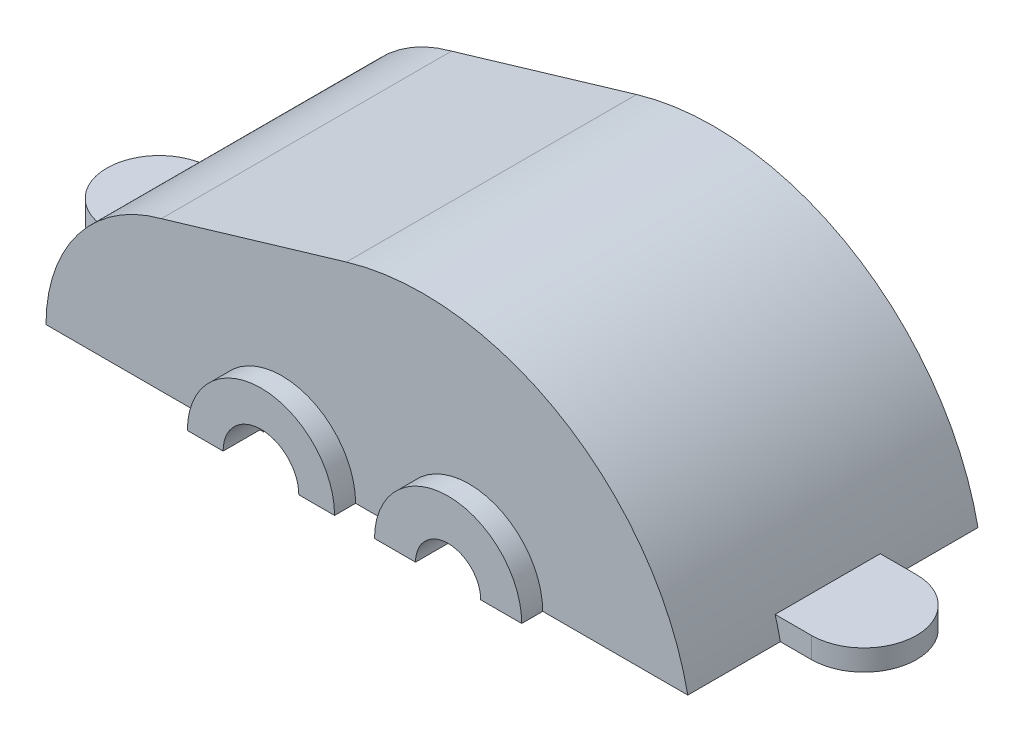
SolidWorks part; units mm, degrees
material "1023 Carbon Steel Sheet (SS)"
ref_plane "Front Plane" through (0, 0, 0) normal (0, 0, 1) x (1, 0, 0)
ref_plane "Top Plane" through (0, 0, 0) normal (0, 1, 0) x (1, 0, 0)
ref_plane "Right Plane" through (0, 0, 0) normal (1, 0, 0) x (0, 0, -1)
sketch "Sketch1" plane through (0, 0, 0) normal (0, 0, 1) x (1, 0, 0)
  line L0 (-31.8564, 122.8324) -> (144.4957, 175.1984)
  line L1 (443.1039, 0) -> (-126.8961, 0)
  line L2 (443.1039, 0) -> (443.1039, 185) construction
  line L3 (443.1039, 185) -> (-126.8961, 185) construction
  line L4 (-126.8961, 185) -> (-126.8961, 0) construction
  arc A0 (-31.8564, 122.8324) -> (-126.8961, 0) centre (0, 0) ccw
  arc A1 (144.4957, 175.1984) -> (443.1039, 0) centre (211.938, -51.9261) cw
  dimension "D1" = 570
  dimension "D2" = 185
extrude "Boss-Extrude1" add sketch "Sketch1" along normal blind 236
shell "Shell1" thickness 20 removed face at (158.1039, 0, 118) outward yes
sketch "Sketch7" plane through (0, 0, 0) normal (0, -1, 0) x (1, 0, 0)
  line L0 (-335.2707, 118) -> (457.2585, 118) construction
  line L1 (-126.8961, 236) -> (443.1039, 236) construction
  line L2 (144.4957, 0) -> (-31.8564, 0) construction
  line L3 (-126.8961, 168) -> (-126.8961, 68.2794)
  line L4 (543.1039, 168) -> (443.1039, 168)
  line L5 (-126.8961, 236) -> (-126.8961, 0) construction
  line L6 (-126.8961, 68.2794) -> (-226.8961, 68.2794)
  line L7 (-226.8961, 68.2794) -> (-226.8961, 168)
  line L8 (-226.8961, 168) -> (-126.8961, 168)
  line L10 (543.1039, 168) -> (543.1039, 68)
  line L11 (443.1039, 236) -> (443.1039, 0) construction
  line L12 (443.1039, 168) -> (443.1039, 68)
  line L13 (443.1039, 68) -> (543.1039, 68)
  dimension "D1" = 100
  dimension "D2" = 100
  dimension "D3" = 100
  dimension "D4" = 100
extrude "Boss-Extrude2" add sketch "Sketch7" against normal blind 20
fillet "Fillet2" 2 edges at (-226.8961, 10, 168) (-226.8961, 10, 68.2794) type full round first side face at (-186.6396, 10.0058, 168) second side face at (-186.6396, 10.0058, 68.2794) middle face at (-226.8961, 10, 118.1397)
sketch "Sketch8" plane through (0, 0, -20) normal (0, 0, -1) x (-1, 0, 0)
  line L0 (146.8961, 0) -> (-463.5621, 0) construction
  line L1 (-41.5621, 0) -> (-113.5621, 0)
  line L2 (-219.5621, 0) -> (-291.5621, 0)
  arc A0 (-219.5621, 0) -> (-291.5621, 0) centre (-255.5621, 0) ccw
  arc A1 (-41.5621, 0) -> (-113.5621, 0) centre (-77.5621, 0) ccw
  dimension "D3" = 72
  dimension "D4" = 72
  dimension "D1" = 208
  dimension "D2" = 178
sketch "Sketch9" plane through (0, 0, 256) normal (0, 0, 1) x (1, 0, 0)
  line L0 (-146.8961, 0) -> (463.5621, 0) construction
  line L1 (286.5621, 0) -> (224.5621, 0)
  line L2 (113.5621, 0) -> (41.5621, 0)
  arc A0 (286.5621, 0) -> (224.5621, 0) centre (255.5621, 0) ccw
  arc A1 (113.5621, 0) -> (41.5621, 0) centre (77.5621, 0) ccw
  dimension "D1" = 72
  dimension "D2" = 62
  dimension "D3" = 208
  dimension "D4" = 178
extrude "Cut-Extrude1" cut sketch "Sketch8" against normal blind 20
extrude "Cut-Extrude2" cut sketch "Sketch9" against normal blind 20
fillet "Fillet3" 2 edges at (543.1039, 10, 168) (543.1039, 10, 68) type full round first side face at (502.1403, 10.0125, 168) second side face at (502.1403, 10.0125, 68) middle face at (543.1039, 10, 118)
sketch "Sketch10" plane through (0, 0, -20) normal (0, 0, -1) x (-1, 0, 0)
  line L0 (-185.5621, 0) -> (-219.5621, 0)
  line L1 (-291.5621, 0) -> (-325.5621, 0)
  arc A0 (-185.5621, 0) -> (-325.5621, 0) centre (-255.5621, 0) ccw
  arc A1 (-219.5621, 0) -> (-291.5621, 0) centre (-255.5621, 0) ccw
extrude "Boss-Extrude3" add sketch "Sketch10" along normal blind 20
ref_plane "Plane1" through (0, 0, 118) normal (0, 0, -1) x (-1, 0, 0)
sketch "Sketch11" plane through (0, 0, -20) normal (0, 0, -1) x (-1, 0, 0)
  line L0 (-147.5621, 0) -> (-113.5621, 0)
  line L1 (-41.5621, 0) -> (-7.5621, 0)
  arc A0 (-41.5621, 0) -> (-113.5621, 0) centre (-77.5621, 0) ccw
  arc A1 (-7.5621, 0) -> (-147.5621, 0) centre (-77.5621, 0) ccw
extrude "Boss-Extrude4" add sketch "Sketch11" along normal blind 20
mirror "Mirror1" about plane through (0, 0, 118) normal (0, 0, -1) of "Boss-Extrude4"
sketch "Sketch12" plane through (0, 0, 256) normal (0, 0, 1) x (1, 0, 0)
  line L0 (325.5621, 0) -> (286.5621, 0)
  line L1 (224.5621, 0) -> (185.5621, 0)
  arc A0 (325.5621, 0) -> (185.5621, 0) centre (255.5621, 0) ccw
  arc A1 (286.5621, 0) -> (224.5621, 0) centre (255.5621, 0) ccw
extrude "Boss-Extrude5" add sketch "Sketch12" along normal blind 20
sketch "Sketch17" plane through (0, 0, 0) normal (0, 0, 1) x (1, 0, 0)
  line L0 (41.5621, 0) -> (45.0621, 0)
  line L1 (110.0621, 0) -> (113.5621, 0)
  line L2 (219.5621, 0) -> (223.0621, 0)
  line L3 (288.0621, 0) -> (291.5621, 0)
  arc A0 (113.5621, 0) -> (41.5621, 0) centre (77.5621, 0) ccw
  arc A1 (110.0621, 0) -> (45.0621, 0) centre (77.5621, 0) ccw
  arc A2 (291.5621, 0) -> (219.5621, 0) centre (255.5621, 0) ccw
  arc A3 (288.0621, 0) -> (223.0621, 0) centre (255.5621, 0) ccw
extrude "Boss-Extrude7" add sketch "Sketch17" against normal blind 5
sketch "Sketch18" plane through (0, 0, 236) normal (0, 0, -1) x (-1, 0, 0)
  line L0 (-286.5621, 0) -> (-283.0621, 0)
  line L1 (-228.0621, 0) -> (-224.5621, 0)
  line L2 (-41.5621, 0) -> (-45.0621, 0)
  line L3 (-110.0621, 0) -> (-113.5621, 0)
  arc A0 (-224.5621, 0) -> (-286.5621, 0) centre (-255.5621, 0) ccw
  arc A1 (-228.0621, 0) -> (-283.0621, 0) centre (-255.5621, 0) ccw
  arc A2 (-41.5621, 0) -> (-113.5621, 0) centre (-77.5621, 0) ccw
  arc A3 (-45.0621, 0) -> (-110.0621, 0) centre (-77.5621, 0) ccw
extrude "Boss-Extrude8" add sketch "Sketch18" against normal blind 5
